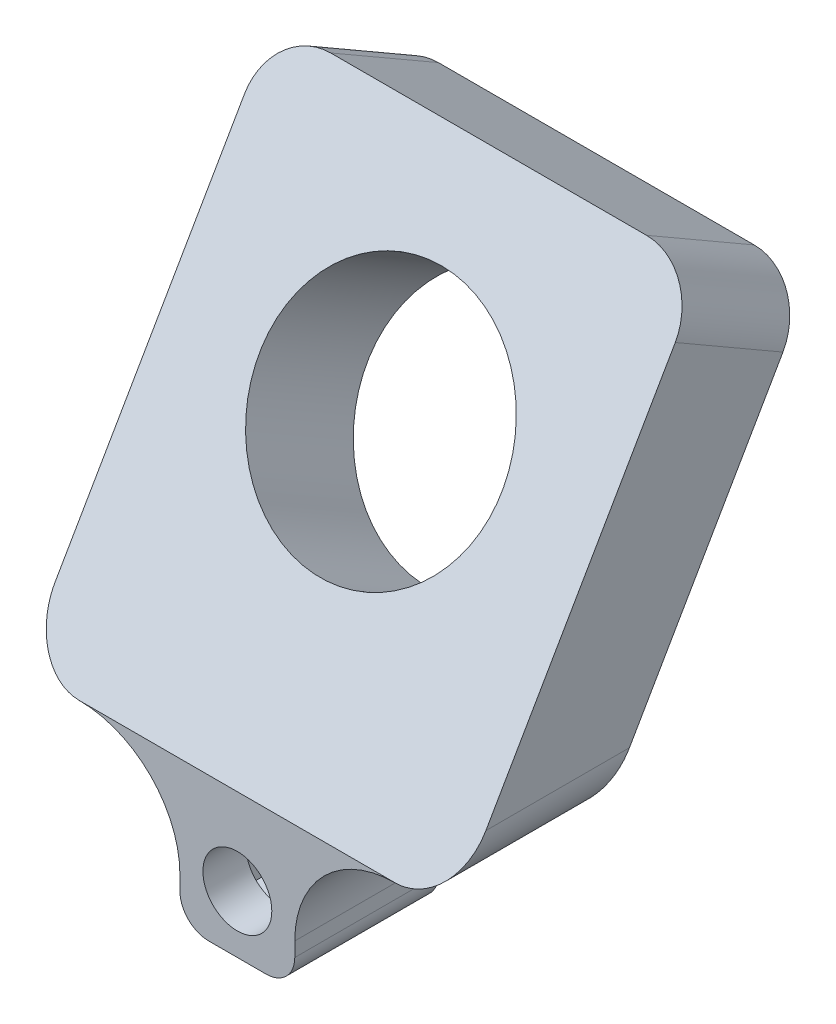
SolidWorks part; units mm, degrees
ref_plane "Front Plane" through (0, 0, 0) normal (0, 0, 1) x (1, 0, 0)
ref_plane "Top Plane" through (0, 0, 0) normal (0, 1, 0) x (1, 0, 0)
ref_plane "Right Plane" through (0, 0, 0) normal (1, 0, 0) x (0, 0, -1)
sketch "Sketch1" plane through (0, 0, 0) normal (0, 0, 1) x (1, 0, 0)
  line L1 (-2, -2.5) -> (2, -2.5)
  line L2 (-2, -2.5) -> (-2, 2.5)
  line L3 (-2, 2.5) -> (2, 2.5)
  line L4 (2, -2.5) -> (2, 2.5)
  line L5 (-2, -2.5) -> (2, 2.5) construction
  line L6 (-2, 2.5) -> (2, -2.5) construction
  point P0 (0, 0)
  dimension "D1" = 4
  dimension "D2" = 5
extrude "Boss-Extrude1" add sketch "Sketch1" along normal mid plane 5
sketch "Sketch2" plane through (0, 0, -2.5) normal (0, 0, -1) x (-1, 0, 0)
  line L1 (-1.5, -2) -> (1.5, -2)
  line L2 (-1.5, -2) -> (-1.5, 1)
  line L3 (-1.5, 1) -> (1.5, 1)
  line L4 (1.5, -2) -> (1.5, 1)
  line L5 (-1.5, -2) -> (1.5, 1) construction
  line L6 (-1.5, 1) -> (1.5, -2) construction
  line L7 (0, 2.75) -> (0, -2.75) construction
  line L10 (-2, 2.5) -> (2, 2.5) construction
  point P0 (0, -0.5)
  point P7 (0, 0)
  dimension "D1" = 3
  dimension "D2" = 3
  dimension "D3" = 1.5
extrude "Cut-Extrude1" cut sketch "Sketch2" against normal blind 3.5
sketch "Sketch3" plane through (0, 0, 0) normal (1, 0, 0) x (0, 0, -1)
  line L0 (-2.5, 2.5) -> (6.25, 17.6554)
  line L1 (6.25, 17.6554) -> (10, 15.4904)
  line L2 (10, 15.4904) -> (2.5, 2.5)
  line L3 (2.5, 2.5) -> (-2.5, 2.5)
  dimension "D1" = 15
  dimension "D2" = 60
extrude "Boss-Extrude2" add sketch "Sketch3" along normal mid plane 15
sketch "Sketch5" plane through (0, -0.4575, -0.7925) normal (0, -0.5, -0.866) x (-1, 0, 0)
  line L0 (0, 6.875) -> (0, -6.875) construction
  line L1 (-7.5, 18.4151) -> (7.5, 18.4151) construction
  point P0 (0, 10.9151)
  point P1 (0, 0)
  dimension "D1" = 7.5
hole_wizard "5/16 Clearance Hole1" positions "Sketch6" profile "Sketch7" hole size "5/16" standard "ANSI Inch" end condition through all
sketch "Sketch6" plane through (0, -0.4575, -0.7925) normal (0, -0.5, -0.866) x (-1, 0, 0)
  point P0 (0, 10.9151)
sketch "Sketch7" plane through (0, 8.9952, -6.25) normal (1, 0, 0) x (0, 0.866, -0.5)
  line L0 (0, 0) -> (0, 11.9078)
  line L1 (0, 11.9078) -> (4.2164, 11.9078)
  line L2 (4.2164, 11.9078) -> (4.2164, 0)
  line L5 (4.2164, 0) -> (0, 0)
  line L11 (0, -6.35) -> (0, 107.95) construction
  dimension "Thru Hole Dia." = 8.4328
  dimension "Thru Hole Depth" = 11.9078
sketch "Sketch8" plane through (0, 0, 2.5) normal (0, 0, 1) x (1, 0, 0)
  line L0 (0, -6.875) -> (0, 6.875) construction
  line L1 (-2, -2.5) -> (2, -2.5) construction
  point P0 (0, -0.5)
  point P1 (0, 0)
  point P3 (1.306, -0.9599)
  dimension "D1" = 2
hole_wizard "M2 Clearance Hole1" positions "Sketch9" profile "Sketch11" hole size "M2" standard "ANSI Metric" end condition through all
sketch "Sketch9" plane through (0, 0, 2.5) normal (0, 0, 1) x (1, 0, 0)
  point P0 (0, -0.5)
sketch "Sketch11" plane through (0, -0.5, 2.5) normal (1, 0, 0) x (0, -1, 0)
  line L0 (0, 0) -> (0, 12.5)
  line L1 (0, 12.5) -> (1.2, 12.5)
  line L2 (1.2, 12.5) -> (1.2, 0)
  line L5 (1.2, 0) -> (0, 0)
  line L11 (0, -6.35) -> (0, 107.95) construction
  dimension "Thru Hole Dia." = 2.4
  dimension "Thru Hole Depth" = 12.5
fillet "Fillet1" radius 3.5 2 edges at (2, 2.5, 0) (-2, 2.5, 0)
fillet "Fillet2" radius 2 4 edges at (-7.5, 16.5729, -8.125) (7.5, 16.5729, -8.125) (7.5, 2.5, 0) (-7.5, 2.5, 0)
fillet "Fillet3" radius 1 2 edges at (2, -2.5, 0) (-2, -2.5, 0)
